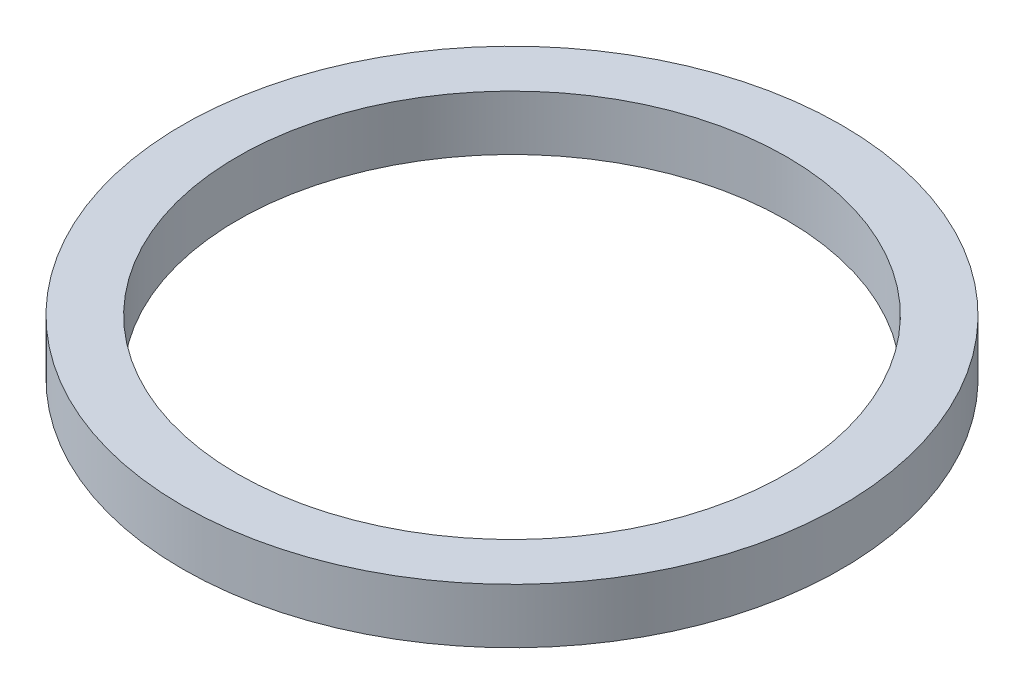
SolidWorks part; units mm, degrees
ref_plane "Front Plane" through (0, 0, 0) normal (0, 0, 1) x (1, 0, 0)
ref_plane "Top Plane" through (0, 0, 0) normal (0, 1, 0) x (1, 0, 0)
ref_plane "Right Plane" through (0, 0, 0) normal (1, 0, 0) x (0, 0, -1)
sketch "Sketch2" plane through (0, 0, 0) normal (0, 1, 0) x (1, 0, 0)
  circle A0 centre (0, 0) radius 0.5
  circle A1 centre (0, 0) radius 0.6
  dimension "D1" = 1
  dimension "D2" = 1.2
extrude "Boss-Extrude1" add sketch "Sketch2" along normal blind 0.05 and the other way blind 0.05
